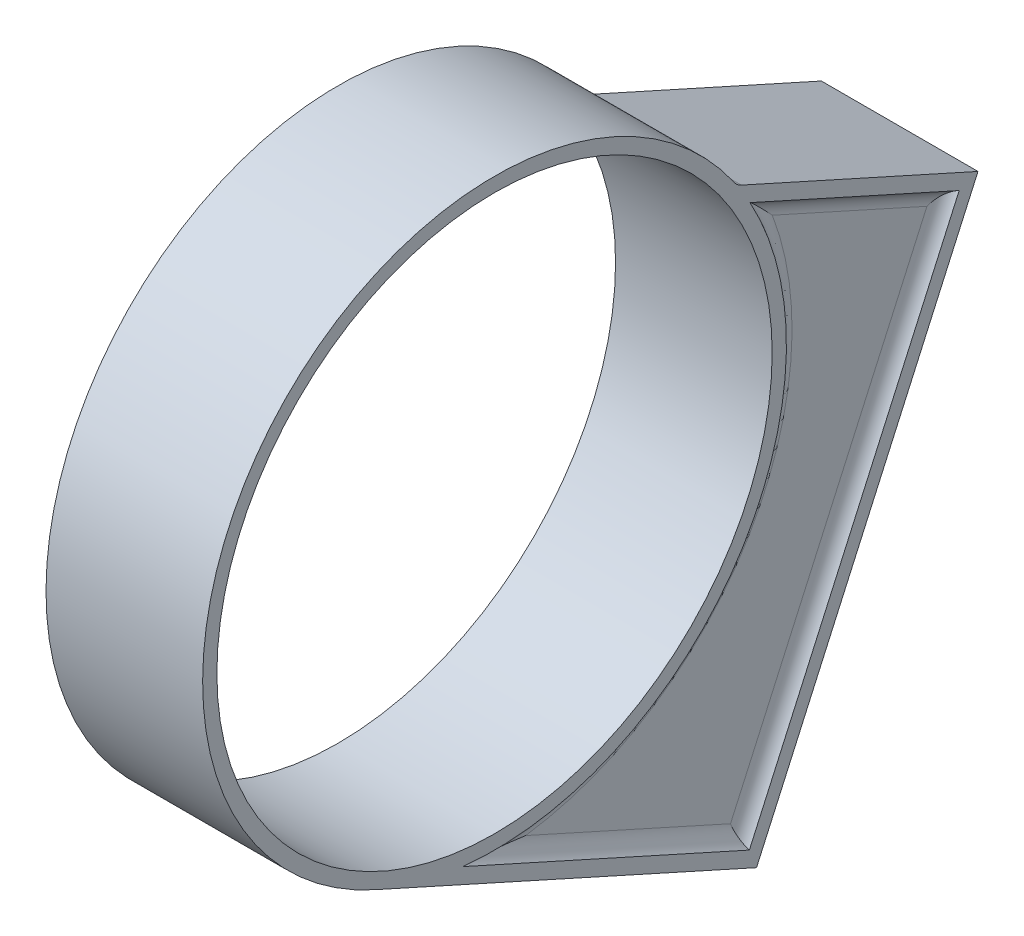
SolidWorks part; units mm, degrees
ref_plane "Front Plane" through (0, 0, 0) normal (0, 0, 1) x (1, 0, 0)
ref_plane "Top Plane" through (0, 0, 0) normal (0, 1, 0) x (1, 0, 0)
ref_plane "Right Plane" through (0, 0, 0) normal (1, 0, 0) x (0, 0, -1)
sketch "Sketch1" plane through (0, 0, 0) normal (1, 0, 0) x (0, 0, -1)
  circle A0 centre (0, 0) radius 195
  circle A1 centre (0, 0) radius 205
  dimension "D1" = 390
  dimension "D2" = 10
extrude "Boss-Extrude1" add sketch "Sketch1" along normal blind 110
sketch "Sketch3" plane through (0, 0, 0) normal (1, 0, 0) x (0, 0, -1)
  line L4 (137.8858, 137.8858) -> (160.9142, 127.0631)
  line L5 (147.9188, 127.0631) -> (167.4354, 118.2809)
  circle A1 centre (0, 0) radius 195 construction
  circle A2 centre (0, 0) radius 205 construction
  arc A3 (167.4354, 118.2809) -> (160.848, 127.0942) centre (0, 0) ccw
  arc A4 (147.9188, 127.0631) -> (137.8858, 137.8858) centre (0, 0) ccw
extrude "Cut-Extrude1" cut sketch "Sketch3" along normal blind 26.1 from offset 41.95 contours A4 L5 A3 L4
sketch "Sketch4" plane through (0, 0, 0) normal (-1, 0, 0) x (0, 0, 1)
  line L1 (-339.5354, 38.0974) -> (-170.1727, 114.3078)
  line L5 (-147.9188, 127.0631) -> (-167.4354, 118.2809) construction
  line L6 (-339.5354, 38.0974) -> (-183.9829, -307.5878)
  line L7 (-183.9829, -307.5878) -> (84.1221, -186.9451)
  circle A0 centre (0, 0) radius 205 construction
  arc A3 (-170.1727, 114.3078) -> (84.1221, -186.9451) centre (0, 0) ccw
  dimension "D1" = 293.9982
  dimension "D2" = 2.5
extrude "Boss-Extrude3" add sketch "Sketch4" against normal up to surface (110 mm away) up to face at (110, 0, -205)
sketch "Sketch5" plane through (0, -120.6427, -268.105) normal (0, -0.4104, -0.9119) x (-1, 0, 0)
  line L4 (-110, 174.071) -> (-110, -205) construction
  line L8 (-20, 154.071) -> (-90, 154.071)
  line L9 (-90, 154.071) -> (-90, -185)
  line L10 (-90, -185) -> (-20, -185)
  line L11 (-20, -185) -> (-20, 154.071)
  line L12 (-30, 154.071) -> (-80, 154.071)
  line L13 (-90, 144.071) -> (-90, -175)
  line L14 (-80, -185) -> (-30, -185)
  line L15 (-20, -175) -> (-20, 144.071)
  circle A0 centre (-90, -185) radius 10
  circle A1 centre (-20, -185) radius 10
  circle A2 centre (-20, 154.071) radius 10
  circle A3 centre (-90, 154.071) radius 10
  dimension "D2" = 20
  dimension "D3" = 20
  dimension "D4" = 20
  dimension "D5" = 20
  dimension "D1" = 20
extrude "Cut-Extrude2" cut sketch "Sketch5" against normal blind 140 contours A0 | A1 | A2 | A3
fillet "Fillet1" radius 12.5 1 edges at (55, 114.3078, -170.1727)
sketch "Sketch6" plane through (110, 0, 0) normal (1, 0, 0) x (0, 0, -1)
  line L6 (326.3126, 33.0817) -> (169.2732, 103.7467)
  line L7 (-80.0186, -177.8258) -> (178.9672, -294.365)
  line L8 (178.9672, -294.365) -> (326.3126, 33.0817)
  line L9 (326.3126, 33.0817) -> (179.4075, 99.1865)
  line L10 (-22.3432, -203.7788) -> (178.9672, -294.365)
  line L11 (178.9672, -294.365) -> (326.3126, 33.0817)
  arc A4 (160.04, 111.4101) -> (169.2732, 103.7467) centre (178.5061, 124.2651) ccw
  arc A5 (160.04, 111.4101) -> (-80.0186, -177.8258) centre (0, 0) ccw
  circle A8 centre (0, 0) radius 205
  arc A9 (-22.3432, -203.7788) -> (179.4075, 99.1865) centre (0, 0) ccw
  dimension "D1" = 10
  dimension "D2" = 10
extrude "Cut-Extrude4" cut sketch "Sketch6" against normal blind 7.5 contours L9 A9 L10 L11
sketch "Sketch7" plane through (0, 0, 0) normal (-1, 0, 0) x (0, 0, 1)
  line L6 (-169.2732, 103.7467) -> (-326.3126, 33.0817)
  line L7 (-326.3126, 33.0817) -> (-178.9672, -294.365)
  line L8 (-178.9672, -294.365) -> (80.0186, -177.8258)
  line L9 (-179.4075, 99.1865) -> (-326.3126, 33.0817)
  line L10 (-326.3126, 33.0817) -> (-178.9672, -294.365)
  line L11 (-178.9672, -294.365) -> (22.3432, -203.7788)
  arc A4 (80.0186, -177.8258) -> (-160.04, 111.4101) centre (0, 0) ccw
  arc A5 (-169.2732, 103.7467) -> (-160.04, 111.4101) centre (-178.5061, 124.2651) ccw
  circle A8 centre (0, 0) radius 205
  arc A9 (-179.4075, 99.1865) -> (22.3432, -203.7788) centre (0, 0) ccw
  dimension "D1" = 10
  dimension "D2" = 10
extrude "Cut-Extrude5" cut sketch "Sketch7" against normal blind 7.5
fillet "Fillet2" radius 12.5 8 edges at (102.5, -249.0719, -78.312) (102.5, -113.6254, -170.6291) (102.5, 66.1341, -252.86) (102.5, -130.6417, -252.6399) (7.5, -249.0719, -78.312) (7.5, -130.6417, -252.6399) (7.5, 66.1341, -252.86) (7.5, -113.6254, -170.6291)
